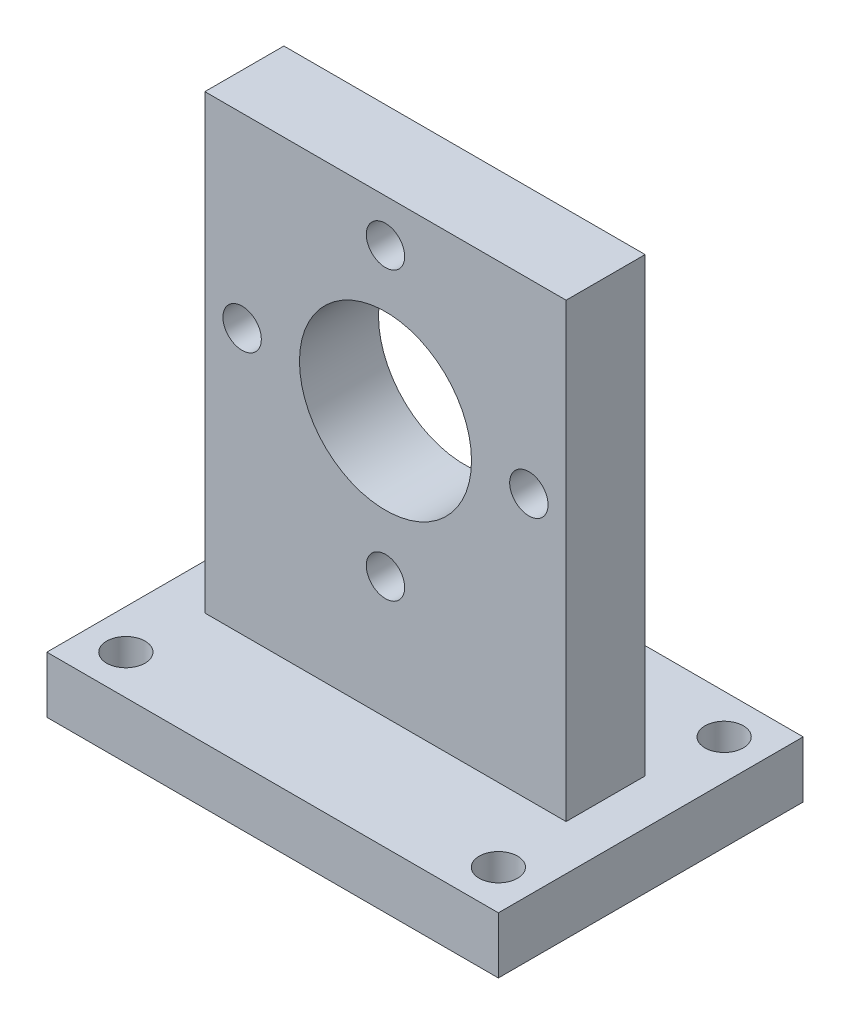
SolidWorks part; units mm, degrees
ref_plane "Front Plane" through (0, 0, 0) normal (0, 0, 1) x (1, 0, 0)
ref_plane "Top Plane" through (0, 0, 0) normal (0, 1, 0) x (1, 0, 0)
ref_plane "Right Plane" through (0, 0, 0) normal (1, 0, 0) x (0, 0, -1)
sketch "Sketch1" plane through (0, 0, 0) normal (0, 1, 0) x (1, 0, 0)
  line L1 (-20, 13.5) -> (20, 13.5)
  line L2 (-20, 13.5) -> (-20, -13.5)
  line L3 (-20, -13.5) -> (20, -13.5)
  line L4 (20, 13.5) -> (20, -13.5)
  line L5 (-20, 13.5) -> (20, -13.5) construction
  line L6 (-20, -13.5) -> (20, 13.5) construction
  line L7 (-16, 3.5) -> (16, 3.5)
  line L8 (-16, 3.5) -> (-16, -3.5)
  line L9 (-16, -3.5) -> (16, -3.5)
  line L10 (16, 3.5) -> (16, -3.5)
  line L11 (-16, 3.5) -> (16, -3.5) construction
  line L12 (-16, -3.5) -> (16, 3.5) construction
  point P0 (0, 0)
  point P6 (0, 0)
  dimension "D1" = 40
  dimension "D2" = 27
  dimension "D3" = 7
  dimension "D4" = 32
extrude "Boss-Extrude1" add sketch "Sketch1" along normal blind 5 contours L10 L7 L8 L9 | L2 L1 L4 L3 region at (0, 0, 0)
extrude "Boss-Extrude2" add sketch "Sketch1<3>" along normal blind 45 contours L10 L7 L8 L9 region at (0, 0, 0)
sketch "Sketch1<3>" plane through (0, 0, 0) normal (0, 1, 0) x (1, 0, 0) same geometry as "Sketch1"
sketch "Sketch2" plane through (0, 0, 3.5) normal (0, 0, 1) x (1, 0, 0)
  line L0 (-20, 5) -> (20, 5) construction
  circle A0 centre (0, 28.5) radius 7.62
  dimension "D1" = 15.24
  dimension "D2" = 23.5
extrude "Cut-Extrude1" cut sketch "Sketch2" against normal up to next
sketch "Sketch4" plane through (0, 0, 3.5) normal (0, 0, 1) x (1, 0, 0)
  line L0 (0, 45) -> (0, 28.5) construction
  line L1 (-16, 45) -> (16, 45) construction
  circle A0 centre (0, 41.2) radius 1.7
  circle A1 centre (0, 28.5) radius 7.62 construction
  circle A2 centre (12.7, 28.5) radius 1.7
  circle A3 centre (0, 15.8) radius 1.7
  circle A4 centre (-12.7, 28.5) radius 1.7
  point P18 (0, 28.5)
  dimension "D2" = 3.4
  dimension "D1" = 12.7
  dimension "D3" = 4
extrude "Cut-Extrude2" cut sketch "Sketch4" against normal up to next
sketch "Sketch5" plane through (0, 5, 0) normal (0, 1, 0) x (1, 0, 0)
  line L1 (-20, 13.5) -> (20, 13.5) construction
  line L2 (-20, 13.5) -> (-20, -13.5) construction
  line L3 (-20, -13.5) -> (20, -13.5) construction
  line L4 (0, 13.5) -> (0, -13.5) construction
  circle A0 centre (-16.5, 10) radius 1.7
  circle A2 centre (-16.5, -10) radius 1.7
  circle A4 centre (16.5, -10) radius 1.7
  circle A5 centre (16.5, 10) radius 1.7
  dimension "D3" = 3.4
  dimension "D1" = 3.5
  dimension "D2" = 3.5
  dimension "D4" = 3.5
extrude "Cut-Extrude3" cut sketch "Sketch5" against normal up to next
